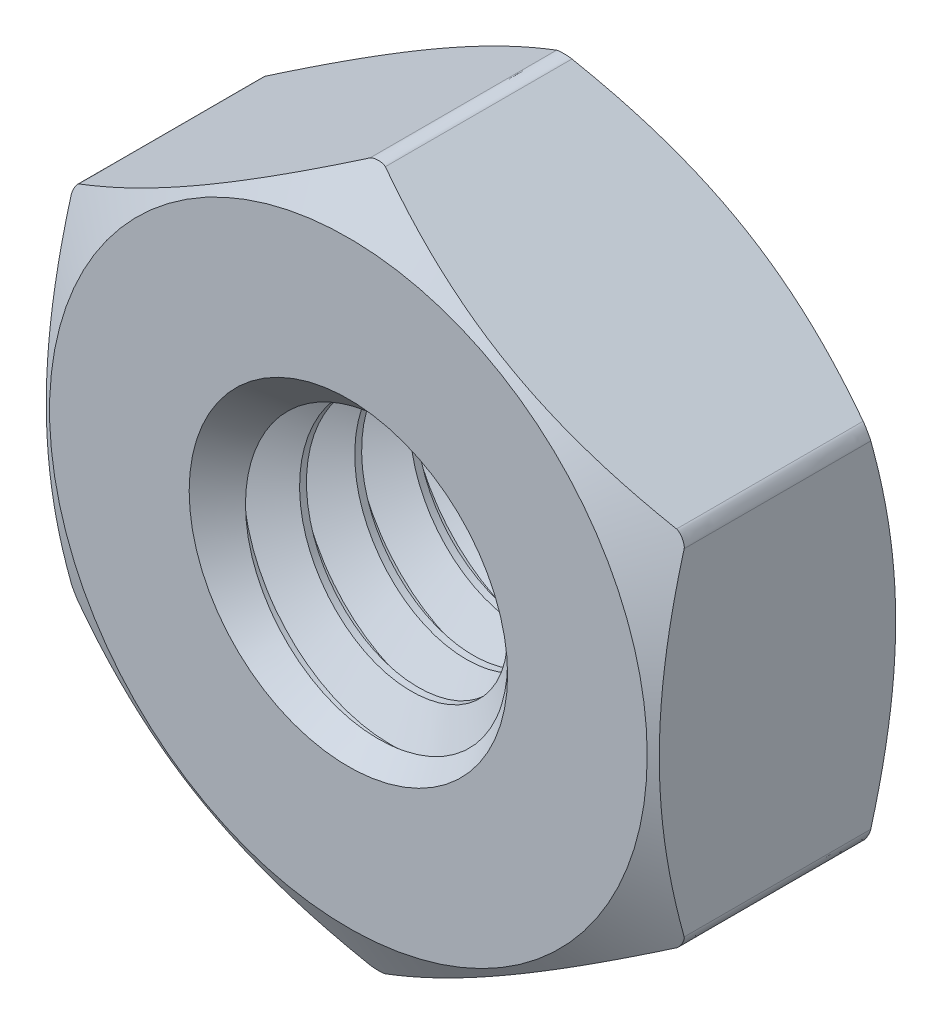
SolidWorks part; units mm, degrees
ref_plane "Front Plane" through (0, 0, 0) normal (0, 0, 1) x (1, 0, 0)
ref_plane "Top Plane" through (0, 0, 0) normal (0, 1, 0) x (1, 0, 0)
ref_plane "Right Plane" through (0, 0, 0) normal (1, 0, 0) x (0, 0, -1)
sketch "Sketch1" plane through (0, 0, 0) normal (0, 0, 1) x (1, 0, 0)
  line L0 (0, -2.8868) -> (0, 2.8868) construction
  line L1 (0, -2.8868) -> (2.5, -1.4434) construction
  line L2 (2.5, -1.4434) -> (2.5, 1.4434) construction
  line L3 (2.5, 1.4434) -> (0, 2.8868) construction
  line L4 (0, 2.8868) -> (-2.5, 1.4434) construction
  line L5 (-2.5, 1.4434) -> (-2.5, -1.4434) construction
  line L6 (-2.5, -1.4434) -> (0, -2.8868) construction
  line L7 (-2.5, 0) -> (2.5, 0) construction
  line L8 (0, 0) -> (0.625, -1.0825) construction
  circle A0 centre (0, 0) radius 2.5 construction
  circle A1 centre (0, 0) radius 1.25 construction
  point P11 (0, 0)
  point P12 (0, -1.25)
  point P14 (1.25, 0)
  point P15 (0, 1.25)
  point P16 (-1.25, 0)
  point P19 (0.625, -1.0825)
  dimension "Thread Diameter" = 2.5
  dimension "Width" = 5
  dimension "D1" = 30
sketch "Sketch2" plane through (0, 0, 0) normal (1, 0, 0) x (0, 0, -1)
  line L0 (0, -2.5) -> (0, 2.5) construction
  line L1 (-1, 2.5) -> (1, 2.5) construction
  line L2 (-1, 2.5) -> (-1, -2.5) construction
  line L3 (-1, -2.5) -> (1, -2.5) construction
  line L4 (1, 2.5) -> (1, -2.5) construction
  line L5 (1, 0) -> (-1, 0) construction
  line L8 (-1, 1.25) -> (1, 1.25) construction
  line L9 (-1, -1.25) -> (1, -1.25) construction
  line L10 (-1.4219, 1.2987) -> (-0.9719, 1.2987) construction
  line L11 (-0.9719, 1.2987) -> (-1.1969, 0.909) construction
  line L12 (-1.1969, 0.909) -> (-1.4219, 1.2987) construction
  line L13 (-1.4078, 1.2744) -> (-0.9859, 1.2744) construction
  line L14 (-1.3937, 1.25) -> (-1, 1.25) construction
  line L15 (-1.225, 0.9577) -> (-1.1687, 0.9577) construction
  line L16 (-1.1969, 0.9577) -> (-1.1969, 0.909) construction
  line L17 (-1.1969, 1.2987) -> (-1.1969, 1.25) construction
  point P8 (0, 0)
  point P29 (-1.1969, 1.2744)
  dimension "Height" = 2
  dimension "Thread Pitch" = 0.45
  dimension "D2" = 0.0563
sketch "Sketch3" plane through (0, 0, 0) normal (0, 0, 1) x (1, 0, 0)
  line L1 (0, -2.8868) -> (2.5, -1.4434)
  line L2 (2.5, -1.4434) -> (2.5, 1.4434)
  line L3 (2.5, 1.4434) -> (0, 2.8868)
  line L4 (0, 2.8868) -> (-2.5, 1.4434)
  line L5 (-2.5, 1.4434) -> (-2.5, -1.4434)
  line L6 (-2.5, -1.4434) -> (0, -2.8868)
  circle A0 centre (0, 0) radius 2.5 construction
  circle A1 centre (0, 0) radius 0.9577
extrude "Boss-Extrude1" add sketch "Sketch3" along normal up to vertex (1 mm away) and the other way up to vertex (1 mm away) up to point (0, 0, 1) other way up to point (0, 0, -1)
sketch "Sketch4" plane through (0, 0, 0) normal (0, 0, 1) x (1, 0, 0)
  circle A0 centre (0, 0) radius 2.4375
  dimension "D1" = 4.875
extrude "Cut-Extrude1" cut sketch "Sketch4" against normal through all draft 60 from vertex flip side to cut starting at point (0, 0, 1)
extrude "Cut-Extrude2" cut sketch "Sketch4<2>" along normal through all draft 60 from vertex flip side to cut starting at point (0, 0, -1)
sketch "Sketch4<2>" plane through (0, 0, 0) normal (0, 0, 1) x (1, 0, 0) same geometry as "Sketch4"
chamfer "Chamfer1" distance 0.2812 angle 45 2 edges at (0.9577, 0, -1) (0.9577, 0, 1)
fillet "Fillet1" radius 0.125 6 edges at (-2.5, -1.4434, 0) (-2.5, 1.4434, 0) (0, -2.8868, 0) (2.5, -1.4434, 0) (0, 2.8868, 0) (2.5, 1.4434, 0) conic rho 0.3
ref_axis "Center Axis 1" through (0, 0, -13.8025) along (0, 0, 1)
sketch "Sketch5" plane through (0, 0, 0) normal (0, 0, 1) x (1, 0, 0)
  circle A0 centre (0, 0) radius 1.25 construction
  circle A1 centre (0, 0) radius 1.25
extrude "Cut-Extrude3" cut sketch "Sketch5" against normal through all both and the other way through all
sketch "Sketch6" plane through (0, 0, 1) normal (0, 0, 1) x (1, 0, 0)
  circle A0 centre (0, 0) radius 1.25 construction
  circle A1 centre (0, 0) radius 1.25
curve "Helix/Spiral1" pitch 0.45 height 2.45 radius 1.25 centre (0, 0, 1) axis (0, 0, -1) start towards (0, 1, 0)
sketch "Sketch7" plane through (0, 0, 0) normal (1, 0, 0) x (0, 0, -1)
  line L0 (-1.4078, 1.2744) -> (-0.9859, 1.2744)
  line L1 (-0.9859, 1.2744) -> (-1.1687, 0.9577)
  line L2 (-1.1687, 0.9577) -> (-1.225, 0.9577)
  line L3 (-1.225, 0.9577) -> (-1.4078, 1.2744)
sweep "Sweep1" add profiles "Sketch7" path "Helix/Spiral1"
sketch "Sketch8" plane through (0, 0, 1) normal (0, 0, 1) x (1, 0, 0)
  circle A0 centre (0, 0) radius 1.2987
extrude "Cut-Extrude4" cut sketch "Sketch8" against normal through all draft 45 and the other way through all
sketch "Sketch9" plane through (0, 0, -1) normal (0, 0, -1) x (-1, 0, 0)
  circle A1 centre (0, 0) radius 1.2987
  circle A2 centre (0, 0) radius 1.2987
  dimension "D1" = 0
extrude "Cut-Extrude5" cut sketch "Sketch9" against normal through all draft 45 and the other way through all
equation "\"D2@Sketch2\" = \"Thread Pitch@Sketch2\" / 8"
equation "\"D1@Chamfer1\"=\"Thread Pitch@Sketch2\"*.625"
equation "\"D1@Sketch4\"=\"Width@Sketch1\"*.975"
equation "\"D1@Fillet1\"=\"Width@Sketch1\"*.025"
equation "\"D4@Helix/Spiral1\"=\"Thread Pitch@Sketch2\""
equation "\"D3@Helix/Spiral1\"=\"Height@Sketch2\"+\"Thread Pitch@Sketch2\""
